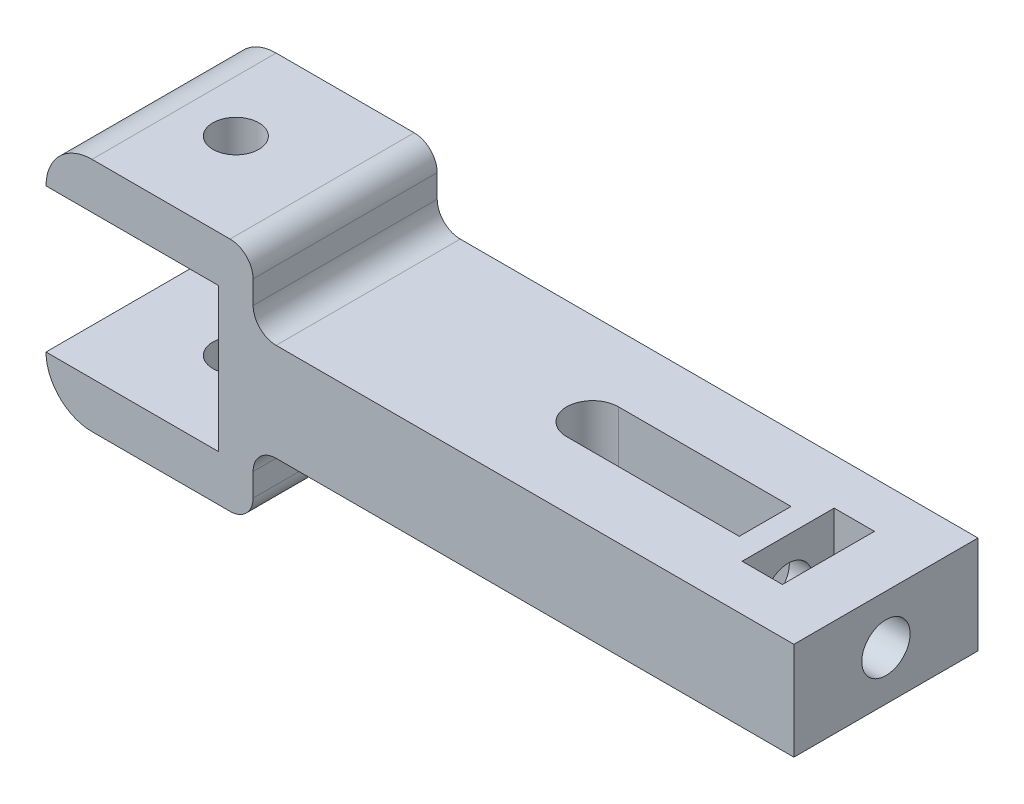
SolidWorks part; units mm, degrees
ref_plane "Front Plane" through (0, 0, 0) normal (0, 0, 1) x (1, 0, 0)
ref_plane "Top Plane" through (0, 0, 0) normal (0, 1, 0) x (1, 0, 0)
ref_plane "Right Plane" through (0, 0, 0) normal (1, 0, 0) x (0, 0, -1)
sketch "Sketch1" plane through (0, 0, 0) normal (0, 0, 1) x (1, 0, 0)
  line L0 (0, 0) -> (-47, 0)
  line L1 (-47, 0) -> (-47, 6)
  line L2 (-47, 6) -> (-65, 6)
  line L3 (-65, 6) -> (-65, 2)
  line L4 (-65, 2) -> (-50, 2)
  line L5 (-50, 2) -> (-50, -10.5)
  line L6 (0, 0) -> (0, -8.5)
  line L7 (0, -4.25) -> (-50, -4.25) construction
  line L8 (-65, -10.5) -> (-50, -10.5)
  line L9 (-65, -14.5) -> (-65, -10.5)
  line L10 (-47, -14.5) -> (-65, -14.5)
  line L11 (-47, -8.5) -> (-47, -14.5)
  line L12 (0, -8.5) -> (-47, -8.5)
  dimension "D1" = 65
  dimension "D2" = 15
  dimension "D3" = 4.25
  dimension "D4" = 6.25
  dimension "D5" = 4
  dimension "D6" = 18
extrude "Boss-Extrude1" add sketch "Sketch1" along normal blind 16
sketch "Sketch2" plane through (0, 0, 0) normal (0, 1, 0) x (1, 0, 0)
  line L0 (0, -8) -> (-47, -8) construction
  line L1 (0, -16) -> (0, 0) construction
  line L2 (-47, -16) -> (-47, 0) construction
  line L4 (-8.5, -4) -> (-5, -4)
  line L5 (-8.5, -4) -> (-8.5, -12)
  line L6 (-8.5, -12) -> (-5, -12)
  line L7 (-5, -4) -> (-5, -12)
  line L8 (-8.5, -4) -> (-5, -12) construction
  line L9 (-8.5, -12) -> (-5, -4) construction
  line L10 (-25.5, -10.25) -> (-10.5, -10.25)
  line L12 (-25.5, -5.75) -> (-10.5, -5.75)
  line L13 (-10.5, -10.25) -> (-10.5, -5.75)
  line L14 (-25.5, -10.25) -> (-10.5, -5.75) construction
  line L15 (-25.5, -5.75) -> (-10.5, -10.25) construction
  arc A0 (-25.5, -5.75) -> (-25.5, -10.25) centre (-25.5, -8) ccw
  point P6 (-6.75, -8)
  point P11 (-18, -8)
  dimension "D7" = 2.25
  dimension "D1" = 8
  dimension "D2" = 3.5
  dimension "D3" = 5
  dimension "D4" = 2
  dimension "D5" = 4.5
  dimension "D6" = 15
extrude "Cut-Extrude1" cut sketch "Sketch2" against normal through all
sketch "Sketch3" plane through (0, 0, 0) normal (1, 0, 0) x (0, 0, -1)
  line L0 (-8, 0) -> (-8, -8.5) construction
  line L1 (-16, 0) -> (0, 0) construction
  line L2 (-16, -8.5) -> (0, -8.5) construction
  circle A0 centre (-8, -4.25) radius 2.1
  dimension "D1" = 4.2
extrude "Cut-Extrude2" cut sketch "Sketch3" against normal up to surface (10.5 mm away) up to face at (-10.5, -4.25, 8)
fillet "Fillet1" radius 2 4 edges at (-47, -8.5, 8) (-47, 6, 8) (-47, 0, 8) (-47, -14.5, 8)
sketch "Sketch4" plane through (0, -10.5, 0) normal (0, 1, 0) x (1, 0, 0)
  line L0 (-65, -8) -> (-49, -8) construction
  line L1 (-65, -16) -> (-65, 0) construction
  line L2 (-49, 0) -> (-49, -16) construction
  circle A0 centre (-57, -8) radius 9
  dimension "D1" = 18
extrude "Cut-Extrude3" cut sketch "Sketch4" along normal up to surface (12.5 mm away) up to face at (-57.5, 2, 8)
sketch "Sketch5" plane through (0, 6, 0) normal (0, 1, 0) x (1, 0, 0)
  line L0 (-65, -8) -> (-49, -8) construction
  line L1 (-65, -16) -> (-65, 0) construction
  line L2 (-49, -16) -> (-49, 0) construction
  circle A0 centre (-56.5, -8) radius 2
  dimension "D1" = 4
  dimension "D2" = 8.5
extrude "Cut-Extrude4" cut sketch "Sketch5" against normal through all
fillet "Fillet2" radius 4 2 edges at (-65, -14.5, 8) (-65, 6, 8)
equation "\"X-ROD-SPACING\"=45"
equation "\"Y-ROD-SPACING\"=75"
equation "\"Z-ROD-SPACING\"=17.5"
equation "\"Y-BED-OFFSET\"=2"
equation "\"Y-BED-ROD-INSET\"=3.5"
equation "\"T-SLOT-NUT-FILLET-RADIUS\"=0.25"
equation "\"T-SLOT-SCREW-SHAFT-RADIUS\"=1.75"
equation "\"T-SLOT-SCREW-SHAFT-CUTOUT-LENGTH\"=10.5"
equation "\"T-SLOT-NUT-DEPTH\"=4.2"
equation "\"T-SLOT-NUT-WIDTH\"=3"
equation "\"T-SLOT-NUT-END-DISTANCE\"=8"
equation "\"ACRYLIC-THICKNESS\"=10"
equation "\"ACRYLIC-TAB-CUTOUT-SIZE\"=\"ACRYLIC-THICKNESS\"+\"ACRYLIC-TAB-TOLERANCE\"*2"
equation "\"ACRYLIC-TAB-WIDTH\"=\"ACRYLIC-THICKNESS\""
equation "\"ACRYLIC-M3-HOLE\"=3.1"
equation "\"SMOOTHROD-CAP-SCREW-DISTANCE\"=20"
equation "\"FRAME-WIDTH-INNER\"=370"
equation "\"NEMA17-HOLE-SPACING\"=31"
equation "\"NEMA17-CENTRAL-CUTOUT\"=22.5"
equation "\"Z-BRACKET-REACH\"=55"
equation "\"TOP-BRACKET-SPACING\"=40"
equation "\"SMOOTHROD-X-LENGTH\"=350"
equation "\"SMOOTHROD-Y-LENGTH\"=350"
equation "\"SMOOTHROD-Z-LENGTH\"=350"
equation "\"SMOOTHROD-TIGHTENING-HEADROOM\"=.25"
equation "\"LEADSCREW-Z-LENGTH\"=300"
equation "\"SCREW-HEAD-RADIUS\"=6"
equation "\"PRINTED-X-SMOOTHROD-DIAMETER\"=8.2"
equation "\"PRINTED-X-SMOOTHROD-CUTOUT\"=10"
equation "\"PRINTED-X-BASE-HEIGHT\"=10"
equation "\"PRINTED-LM8UU-CUTOUT-SIZE\"=15.25"
equation "\"PRINTED-LM8UU-CUTOUT-LENGTH\"=24.5"
equation "\"PRINTED-X-IDLER-HEIGHT\"=16"
equation "\"D1@Boss-Extrude1\"=\"PRINTED-X-IDLER-HEIGHT\""
